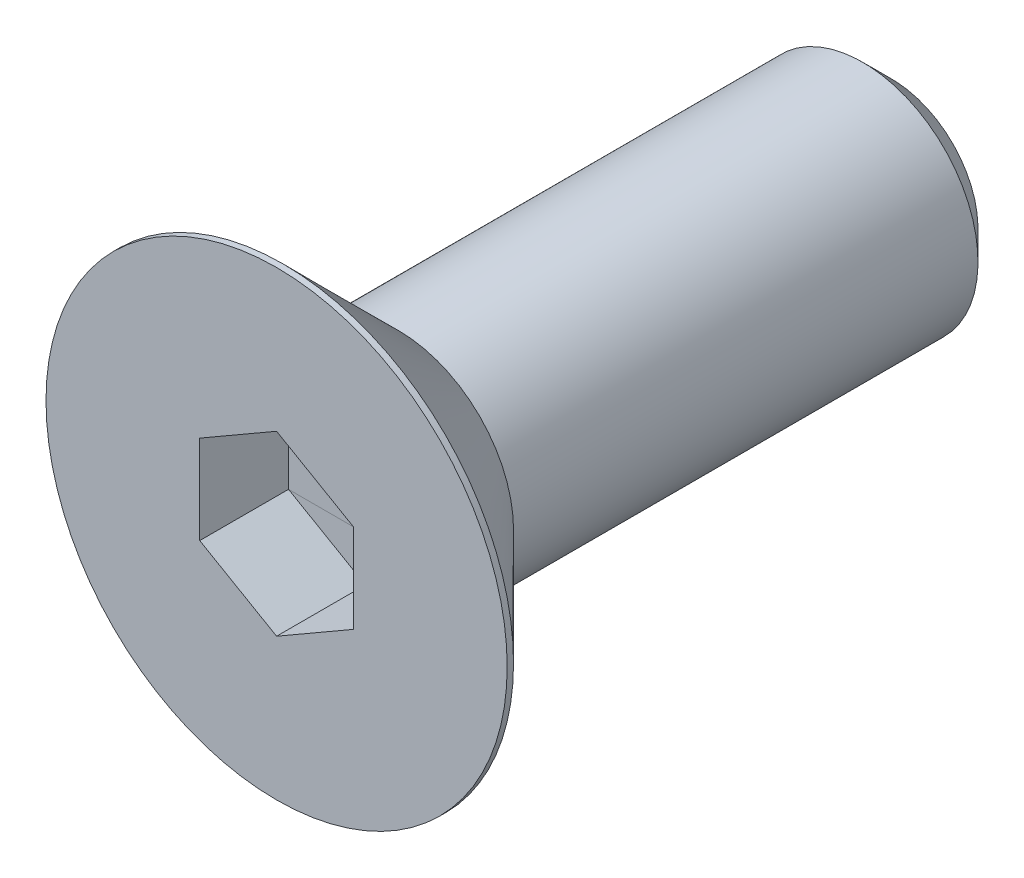
SolidWorks part; units mm, degrees
ref_plane "Front" through (0, 0, 0) normal (0, 0, 1) x (1, 0, 0)
ref_plane "Top" through (0, 0, 0) normal (0, 1, 0) x (1, 0, 0)
ref_plane "Right" through (0, 0, 0) normal (1, 0, 0) x (0, 0, -1)
sketch "Sketch11" plane through (0, 0, 0) normal (1, 0, 0) x (0, 0, -1)
  line L0 (-8, 6) -> (8, 6) construction
  line L5 (-8, 6) -> (-8, -6) construction
  line L6 (8, 3) -> (8, -3) construction
  line L7 (-7.99, 2) -> (-7.99, -2) construction
  line L8 (7.9375, 3.1083) -> (8.9375, 3.1083) construction
  line L9 (8.9375, 3.1083) -> (8.4375, 2.2422) construction
  line L10 (8.4375, 2.2422) -> (7.9375, 3.1083) construction
  line L11 (8.375, 2.3505) -> (8.5, 2.3505) construction
  line L12 (8.4375, 2.3505) -> (8.4375, 2.2422) construction
  line L13 (7.9687, 3.0541) -> (8.9062, 3.0541) construction
  line L14 (8.4375, 3.1083) -> (8.4375, 3) construction
  line L15 (8, 3) -> (8.875, 3) construction
  line L17 (-7.835, 6) -> (-1.835, 0) construction
  line L18 (-1.835, 0) -> (-7.835, -6) construction
  point P3 (-4.7, 6)
  point P8 (0, 6)
  point P21 (8.4375, 3.0541)
  point P26 (-8, 0)
  point P28 (-7.99, 0)
  point P29 (8, 0)
  dimension "Length" = 16
  dimension "Head Diameter" = 12
  dimension "Thread Major Diameter" = 6
  dimension "Head Height" = 3.3
  dimension "Drive Size" = 4
  dimension "Thread Pitch" = 1
  dimension "D1" = 0.125
  dimension "D2" = 0.01
  dimension "D3" = 0.165
  dimension "Countersink Angle" = 90
sketch "Sketch1" plane through (0, 0, 0) normal (1, 0, 0) x (0, 0, -1)
  line L2 (-4.7, 3) -> (8, 3)
  line L3 (8, 3) -> (8, 0)
  line L4 (-5.69, 3) -> (-5.69, 0)
  line L5 (-4.7, 3) -> (-5.69, 3)
  line L6 (-8, 6) -> (-8, -6) construction
  line L7 (8, 3) -> (8, -3) construction
  line L8 (-5.69, 0) -> (8, 0)
  dimension "D1" = 2.31
revolve "Revolve1" add sketch "Sketch1" angle 360 mid plane about L8
chamfer "Chamfer1" distance 0.75 angle 45 1 edges at (0, -3, -8)
sketch "Sketch7" plane through (0, 0, 0) normal (1, 0, 0) x (0, 0, -1)
  line L2 (-8, 6) -> (-7.835, 6)
  line L5 (-4.7, 2.865) -> (-4.7, 0)
  line L6 (-8, 6) -> (-8, 0)
  line L8 (-8, 6) -> (-8, -6) construction
  line L9 (-8, 0) -> (-4.7, 0)
  line L12 (-7.835, 6) -> (-4.7, 2.865)
  line L13 (-7.835, 6) -> (-1.835, 0) construction
revolve "Revolve2" add sketch "Sketch7" angle 360 mid plane about L9 region at (0, 2.3546, 6.5497)
ref_plane "Plane1" through (0, 0, 4.7) normal (0, 0, 1) x (1, 0, 0)
sketch "Sketch5" plane through (0, 0, 8) normal (0, 0, 1) x (1, 0, 0)
  line L1 (2, -1.1547) -> (2, 1.1547)
  line L2 (2, 1.1547) -> (0, 2.3094)
  line L3 (0, 2.3094) -> (-2, 1.1547)
  line L4 (-2, 1.1547) -> (-2, -1.1547)
  line L5 (-2, -1.1547) -> (0, -2.3094)
  line L6 (0, -2.3094) -> (2, -1.1547)
  circle A0 centre (0, 0) radius 2 construction
extrude "Cut-Extrude2" cut sketch "Sketch5" against normal blind 2.31
sketch "Sketch6" plane through (0, 0, 8) normal (0, 0, -1) x (-1, 0, 0)
  circle A0 centre (0, 0) radius 2.3094
extrude "Cut-Extrude3" [suppressed] cut sketch "Sketch6" along normal blind 2.31 draft 45
sketch "Sketch12" [suppressed] plane through (0, 0, -8) normal (0, 0, -1) x (-1, 0, 0)
  circle A0 centre (0, 0) radius 3 construction
  circle A1 centre (0, 0) radius 3
curve "Helix/Spiral1" [suppressed] pitch 1 height 16 turns 16
sketch "Sketch13" [suppressed] plane through (0, 0, 0) normal (1, 0, 0) x (0, 0, -1)
  line L0 (7.9687, 3.0541) -> (8.9062, 3.0541)
  line L1 (8.9062, 3.0541) -> (8.5, 2.3505)
  line L2 (8.5, 2.3505) -> (8.375, 2.3505)
  line L3 (8.375, 2.3505) -> (7.9687, 3.0541)
sweep "Cut-Sweep1" [suppressed] cut profiles "Sketch13" path "Helix/Spiral1"
combine bodies "Combine1" [suppressed] operation type add bodies to combine 113 127
equation "\"D1@Chamfer1\"=\"Thread Pitch@Sketch11\" * .75"
equation "\"D1@Cut-Extrude2\"= \"Head Height@Sketch11\" * .7"
equation "\"D1@Cut-Extrude3\" = \"D1@Cut-Extrude2\""
equation "\"D1@Sketch11\"=\"Thread Pitch@Sketch11\"/8"
equation "\"D3@Sketch11\"=\"Head Height@Sketch11\"*.05"
equation "\"D4@Helix/Spiral1\"=\"Thread Pitch@Sketch11\""
equation "\"D1@Sketch1\"=\"Head Height@Sketch11\"*.7"
equation "\"D3@Helix/Spiral1\"=\"Length@Sketch11\""
